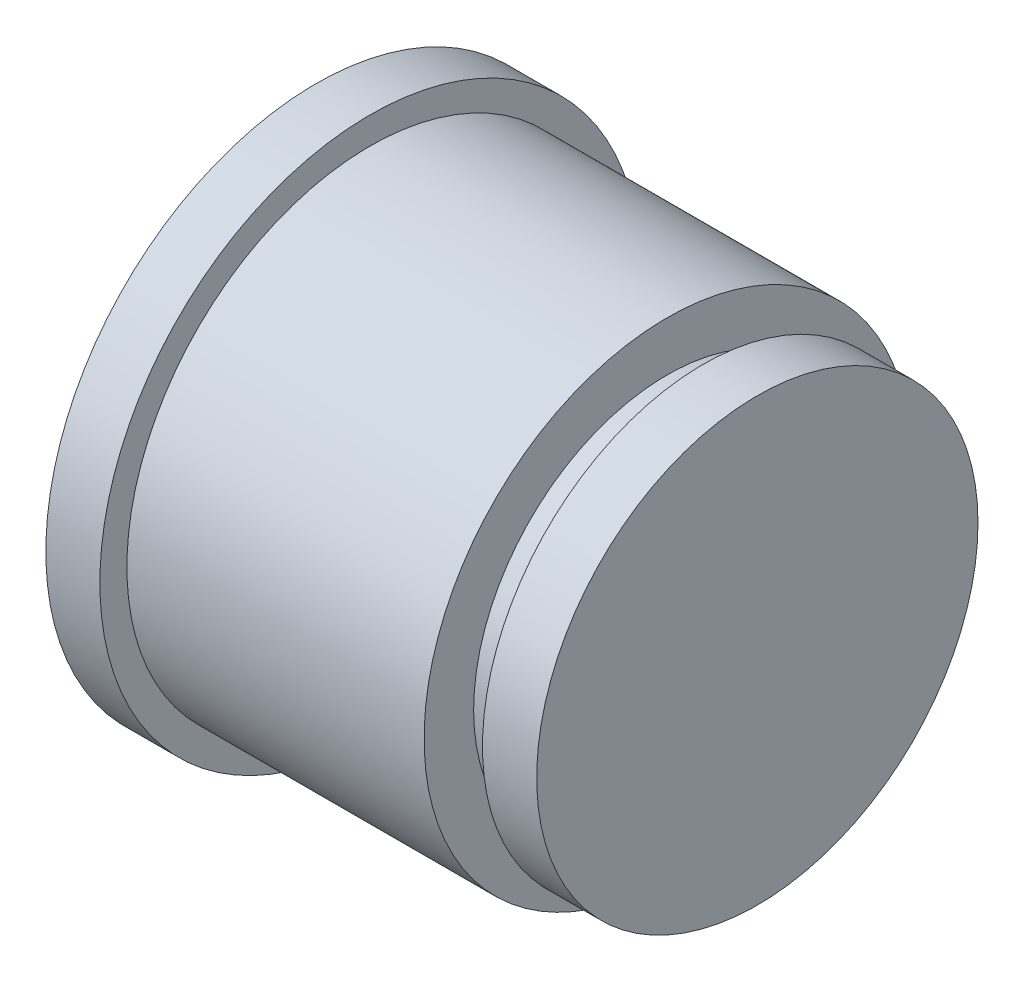
SolidWorks part; units mm, degrees
ref_plane "Front Plane" through (0, 0, 0) normal (0, 0, 1) x (1, 0, 0)
ref_plane "Top Plane" through (0, 0, 0) normal (0, 1, 0) x (1, 0, 0)
ref_plane "Right Plane" through (0, 0, 0) normal (1, 0, 0) x (0, 0, -1)
sketch "Sketch1" plane through (0, 0, 0) normal (1, 0, 0) x (0, 0, -1)
  circle A0 centre (0, 0) radius 30
  dimension "D1" = 60
extrude "bigLip" add sketch "Sketch1" along normal blind 6
sketch "Sketch2" plane through (6, 0, 0) normal (1, 0, 0) x (0, 0, -1)
  circle A0 centre (0, 0) radius 27
  dimension "D1" = 54
extrude "innerTube" add sketch "Sketch2" along normal blind 33
sketch "Sketch3" plane through (39, 0, 0) normal (1, 0, 0) x (0, 0, -1)
  circle A0 centre (0, 0) radius 21.5
  dimension "D1" = 43
extrude "connection" add sketch "Sketch3" along normal blind 4
sketch "Sketch4" plane through (43, 0, 0) normal (1, 0, 0) x (0, 0, -1)
  circle A0 centre (0, 0) radius 24.5
  dimension "D1" = 49
extrude "smallLip" add sketch "Sketch4" along normal blind 6
chamfer "Chamfer1" distance 0.55 angle 80 1 edges at (43, 0, -21.5) first distance on face at (43, 0, -21.5)
sketch "Sketch5" plane through (49, 0, 0) normal (1, 0, 0) x (0, 0, -1)
  circle A0 centre (0, 0) radius 22.5
  dimension "D1" = 45
curve "Helix/Spiral1"
